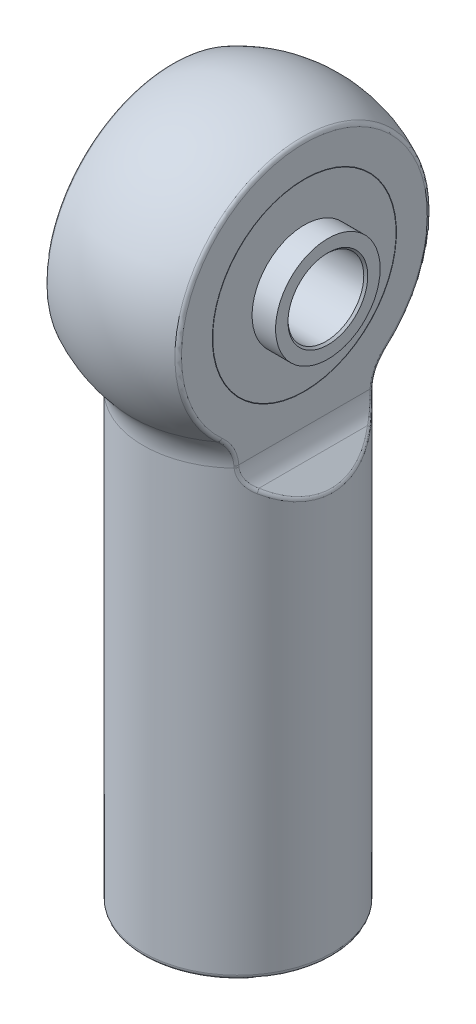
SolidWorks part; units mm, degrees
other "C-Rev Body"
material "AISI 1020"
ref_plane "Front Plane" through (0, 0, 0) normal (0, 0, 1) x (1, 0, 0)
ref_plane "Top Plane" through (0, 0, 0) normal (0, 1, 0) x (1, 0, 0)
ref_plane "Right Plane" through (0, 0, 0) normal (1, 0, 0) x (0, 0, -1)
sketch "Sketch1" plane through (0, 0, 0) normal (0, 0, 1) x (1, 0, 0)
  line L0 (0, 0) -> (0, -47.625) construction
  line L1 (-4.8895, -47.625) -> (-7.9375, -47.625)
  line L2 (-7.9375, -47.625) -> (-7.9375, -8.8829)
  line L3 (0, -14.0626) -> (0, 11.9126)
  line L4 (0, -14.0626) -> (-4.8895, -16.6624)
  line L5 (-4.8895, -16.6624) -> (-4.8895, -47.625)
  arc A0 (0, 11.9126) -> (-7.9375, -8.8829) centre (0, 0) ccw
  dimension "D2" = 23.8252
  dimension "D1" = 47.625
  dimension "D3" = 15.875
  dimension "D4" = 30.9626
  dimension "D7" = 118
  dimension "D8" = 9.779
revolve "Revolve1" add sketch "Sketch1" angle 360 about L0
sketch "Sketch2" plane through (0, 0, 0) normal (0, 0, 1) x (1, 0, 0)
  line L0 (0, 0) -> (0, 10.8779) construction
  line L1 (5.5626, 10.5341) -> (5.5626, -10.2819)
  line L2 (-5.5626, 10.5341) -> (-5.5626, -10.2819)
  line L4 (-6.3065, -12.078) -> (-7.9375, -13.7089)
  line L5 (-7.9375, -8.8829) -> (-7.9375, -47.625) construction
  line L6 (-7.9375, -8.8829) -> (-7.9375, -13.7089)
  line L7 (6.3065, -12.078) -> (7.9375, -13.7089)
  line L8 (7.9375, -8.8829) -> (7.9375, -13.7089)
  arc A0 (7.9375, -8.8829) -> (-7.9375, -8.8829) centre (0, 0) ccw construction
  arc A1 (7.9375, -8.8829) -> (5.5626, 10.5341) centre (0, 0) ccw
  arc A2 (-5.5626, 10.5341) -> (-7.9375, -8.8829) centre (0, 0) ccw
  arc A3 (5.5626, -10.2819) -> (6.3065, -12.078) centre (8.1026, -10.2819) ccw
  arc A4 (-5.5626, -10.2819) -> (-6.3065, -12.078) centre (-8.1026, -10.2819) cw
  point P10 (5.5626, -11.334)
  point P17 (-5.5626, -11.334)
  dimension "D4" = 2.54
  dimension "D1" = 11.1252
  dimension "D2" = 45
  dimension "D3" = 4.826
extrude "Extrude1" cut sketch "Sketch2" against normal through all and the other way through all
sketch "Sketch3" plane through (0, 0, 0) normal (1, 0, 0) x (0, 0, -1)
  circle A0 centre (0, 0) radius 4.3815
  dimension "D1" = 8.763
extrude "Extrude2" add sketch "Sketch3" along normal blind 7.5311 and the other way blind 7.5311
hole_wizard "#11 (0.191) Diameter Hole1" positions "Sketch5" profile "Sketch4" hole size "#11" standard "ANSI Inch" end condition up to next
sketch "Sketch5" plane through (7.5311, 0, 0) normal (-1, 0, 0) x (0, 0, 1)
  point P0 (0, 0)
sketch "Sketch4" plane through (7.5311, 0, 0) normal (0, 1, 0) x (0, 0, -1)
  line L0 (0, 0) -> (0, 15.0622)
  line L1 (0, 15.0622) -> (3.3421, 15.0622)
  line L2 (3.175, 14.8951) -> (3.175, 0.1671)
  line L3 (3.175, 0.1671) -> (3.3421, 0)
  line L5 (3.3421, 0) -> (0, 0)
  line L6 (-3.175, 0.1671) -> (-3.3421, 0) construction
  line L7 (3.3421, 15.0622) -> (3.175, 14.8951)
  line L8 (-3.3421, 15.0622) -> (-3.175, 14.8951) construction
  line L11 (0, -6.35) -> (0, 107.95) construction
  dimension "Thru Hole Dia." = 6.35
  dimension "Thru Hole Depth" = 15.0622
  dimension "Near C'Sink Dia." = 6.6842
  dimension "Near C'Sink Angle" = 90
  dimension "Far C'Sink Dia." = 6.6842
  dimension "Far C'Sink Angle" = 90
fillet "Fillet2" radius 3.81 2 edges at (0, -8.8829, 7.9375) (0, -8.8829, -7.9375)
fillet "Fillet1" radius 0.381 17 edges at (5.6187, -10.813, 5.6066) (7.9375, -13.7089, 0) (5.8915, -11.5319, -5.3193) (-5.8915, -11.5319, 5.3193) (-7.9375, -13.7089, 0) (-5.6187, -10.813, -5.6066) (-5.5626, 10.5341, 0) (5.5626, 10.5341, 0) (-7.9375, -47.625, 0) (-5.5626, -9.2279, 5.9411) (-5.5626, -8.9029, -6.1137) (5.5626, -9.2279, -5.9411) (5.5626, -8.9029, 6.1137)
sketch "Sketch6" plane through (0, 0, 0) normal (1, 0, 0) x (0, 0, -1)
  line L0 (-11.8595, 0) -> (11.8595, 0) construction
  line L1 (-9.5123, 0) -> (-9.4869, 0)
  line L2 (9.4869, 0) -> (9.5123, 0)
  arc A1 (9.4869, 0) -> (-9.4869, 0) centre (0, 0) ccw
  arc A2 (9.5123, 0) -> (-9.5123, 0) centre (0, 0) ccw
  circle A3 centre (0, 0) radius 9.4869 construction
  circle A4 centre (0, 0) radius 9.5123 construction
  dimension "D1" = 18.9738
  dimension "D2" = 0.0254
revolve "Cut-Revolve1" cut sketch "Sketch6" angle 360 about L2
